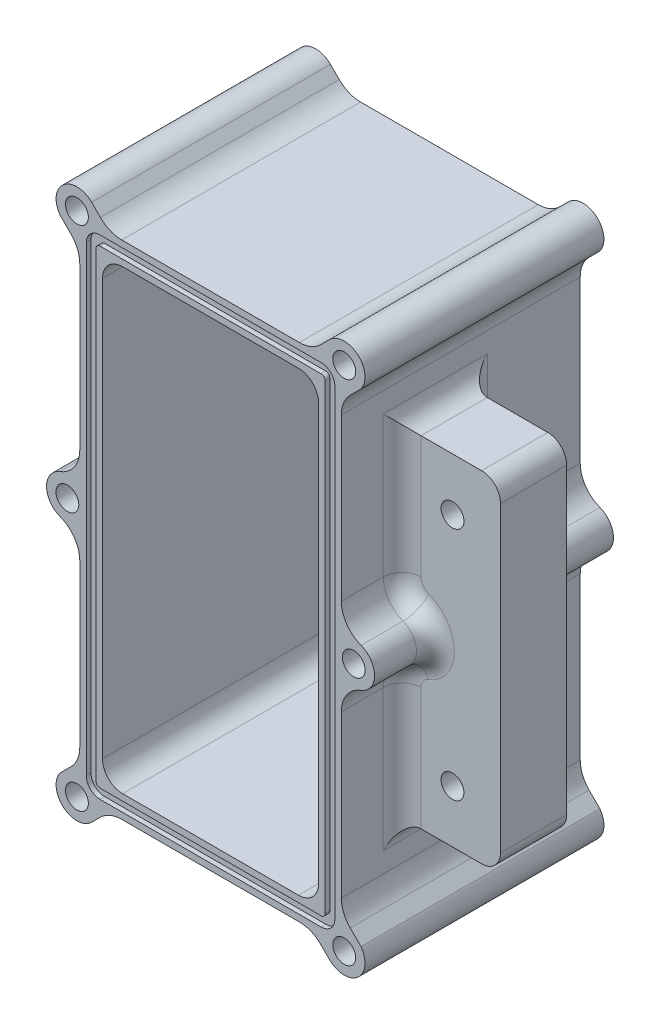
SolidWorks part; units mm, degrees
material "ABS"
ref_plane "X-Y Datum" through (0, 0, 0) normal (0, 0, 1) x (1, 0, 0)
ref_plane "X-Z Datum" through (0, 0, 0) normal (0, 1, 0) x (1, 0, 0)
ref_plane "Y-Z Datum" through (0, 0, 0) normal (1, 0, 0) x (0, 0, -1)
sketch "Sketch2" plane through (0, 0, 0) normal (0, 0, 1) x (1, 0, 0)
  line L1 (-28.575, 60.325) -> (28.575, 60.325)
  line L2 (-28.575, 60.325) -> (-28.575, -60.325)
  line L3 (-28.575, -60.325) -> (28.575, -60.325)
  line L4 (28.575, 60.325) -> (28.575, -60.325)
  line L5 (-28.575, 60.325) -> (28.575, -60.325) construction
  line L6 (-28.575, -60.325) -> (28.575, 60.325) construction
  point P0 (0, 0)
  dimension "D1" = 57.15
  dimension "D2" = 120.65
extrude "Boss-Extrude1" add sketch "Sketch2" along normal mid plane 57.15
shell "Shell1" thickness 6 removed face at (0, 0, 28.575) outward yes
sketch "Sketch3" plane through (0, 0, -28.575) normal (0, 0, 1) x (1, 0, 0)
  line L4 (28.575, -60.325) -> (28.575, 60.325)
  line L5 (28.575, 60.325) -> (-28.575, 60.325)
  line L6 (-28.575, 60.325) -> (-28.575, -60.325)
  line L7 (-28.575, -60.325) -> (28.575, -60.325)
  line L8 (28.575, -60.325) -> (28.575, 60.325)
  line L9 (28.575, 60.325) -> (-28.575, 60.325)
  line L10 (-28.575, 60.325) -> (-28.575, -60.325)
  line L11 (-28.575, -60.325) -> (28.575, -60.325)
  dimension "D1" = 0
extrude "Cut-Extrude1" cut sketch "Sketch3" against normal blind 50.8
fillet "Fillet1" radius 5.334 8 edges at (-34.575, -66.325, -3) (34.575, -66.325, -3) (34.575, 66.325, -3) (-34.575, 66.325, -3) (-28.575, -60.325, -3) (28.575, -60.325, -3) (-28.575, 60.325, -3) (28.575, 60.325, -3)
sketch "Sketch5" plane through (0, 0, -34.575) normal (0, 0, -1) x (-1, 0, 0)
  line L19 (-29.241, -64.6077) -> (29.241, -64.6077)
  line L20 (32.8577, -60.991) -> (32.8577, 60.991)
  line L21 (29.241, 64.6077) -> (-29.241, 64.6077)
  line L22 (-32.8577, 60.991) -> (-32.8577, -60.991)
  line L23 (-29.241, -63.325) -> (29.241, -63.325)
  line L24 (31.575, -60.991) -> (31.575, 60.991)
  line L25 (29.241, 63.325) -> (-29.241, 63.325)
  line L26 (-31.575, 60.991) -> (-31.575, -60.991)
  line L27 (-29.241, -63.325) -> (29.241, -63.325) construction
  line L28 (31.575, -60.991) -> (31.575, 60.991) construction
  line L29 (29.241, 63.325) -> (-29.241, 63.325) construction
  line L30 (-31.575, 60.991) -> (-31.575, -60.991) construction
  line L31 (-30.2923, 60.991) -> (-30.2923, -60.991)
  line L32 (-29.241, -62.0423) -> (29.241, -62.0423)
  line L33 (30.2923, -60.991) -> (30.2923, 60.991)
  line L34 (29.241, 62.0423) -> (-29.241, 62.0423)
  arc A17 (29.241, -64.6077) -> (32.8577, -60.991) centre (29.241, -60.991) ccw
  arc A18 (32.8577, 60.991) -> (29.241, 64.6077) centre (29.241, 60.991) ccw
  arc A19 (-29.241, 64.6077) -> (-32.8577, 60.991) centre (-29.241, 60.991) ccw
  arc A20 (-32.8577, -60.991) -> (-29.241, -64.6077) centre (-29.241, -60.991) ccw
  arc A21 (-31.575, -60.991) -> (-29.241, -63.325) centre (-29.241, -60.991) ccw
  arc A22 (29.241, -63.325) -> (31.575, -60.991) centre (29.241, -60.991) ccw
  arc A23 (31.575, 60.991) -> (29.241, 63.325) centre (29.241, 60.991) ccw
  arc A24 (-29.241, 63.325) -> (-31.575, 60.991) centre (-29.241, 60.991) ccw
  arc A25 (-31.575, -60.991) -> (-29.241, -63.325) centre (-29.241, -60.991) ccw construction
  arc A26 (29.241, -63.325) -> (31.575, -60.991) centre (29.241, -60.991) ccw construction
  arc A27 (31.575, 60.991) -> (29.241, 63.325) centre (29.241, 60.991) ccw construction
  arc A28 (-29.241, 63.325) -> (-31.575, 60.991) centre (-29.241, 60.991) ccw construction
  arc A29 (-29.241, 62.0423) -> (-30.2923, 60.991) centre (-29.241, 60.991) ccw
  arc A30 (-30.2923, -60.991) -> (-29.241, -62.0423) centre (-29.241, -60.991) ccw
  arc A31 (29.241, -62.0423) -> (30.2923, -60.991) centre (29.241, -60.991) ccw
  arc A32 (30.2923, 60.991) -> (29.241, 62.0423) centre (29.241, 60.991) ccw
  dimension "D1" = 3
  dimension "D2" = 1.2827
  dimension "D3" = 1.2827
extrude "Cut-Extrude2" cut sketch "Sketch5" against normal blind 1.2446
ref_plane "Plane1" through (0, 0, -3) normal (0, 0, 1) x (1, 0, 0)
sketch "Sketch6" plane through (0, 0, -34.575) normal (0, 0, -1) x (-1, 0, 0)
  line L0 (29.9844, 61.7344) -> (31.7984, 63.5484)
  line L1 (31.7984, 63.5484) -> (35.3339, 67.0839)
  line L2 (39.7675, 63.8292) -> (34.575, 58.6367)
  line L3 (34.575, 60.991) -> (34.575, -60.991) construction
  line L4 (31.4448, 70.973) -> (26.7968, 66.325)
  line L5 (-29.241, 66.325) -> (29.241, 66.325) construction
  line L10 (-29.241, -66.325) -> (29.241, -66.325)
  line L11 (34.575, -60.991) -> (34.575, 60.991)
  line L12 (29.241, 66.325) -> (-29.241, 66.325)
  line L13 (-34.575, 60.991) -> (-34.575, -60.991)
  line L14 (-29.241, -66.325) -> (29.241, -66.325)
  line L15 (34.575, -60.991) -> (34.575, 60.991)
  line L16 (29.241, 66.325) -> (-29.241, 66.325)
  line L17 (-34.575, 60.991) -> (-34.575, -60.991)
  arc A0 (30.2923, 60.991) -> (29.241, 62.0423) centre (29.241, 60.991) ccw construction
  arc A1 (32.8577, 60.991) -> (29.241, 64.6077) centre (29.241, 60.991) ccw construction
  circle A2 centre (35.3339, 67.0839) radius 3.025
  circle A3 centre (35.3339, 67.0839) radius 5.5
  arc A8 (29.241, -66.325) -> (34.575, -60.991) centre (29.241, -60.991) ccw
  arc A9 (34.575, 60.991) -> (29.241, 66.325) centre (29.241, 60.991) ccw
  arc A10 (-29.241, 66.325) -> (-34.575, 60.991) centre (-29.241, 60.991) ccw
  arc A11 (-34.575, -60.991) -> (-29.241, -66.325) centre (-29.241, -60.991) ccw
  arc A12 (29.241, -66.325) -> (34.575, -60.991) centre (29.241, -60.991) ccw
  arc A13 (34.575, 60.991) -> (29.241, 66.325) centre (29.241, 60.991) ccw
  arc A14 (-29.241, 66.325) -> (-34.575, 60.991) centre (-29.241, 60.991) ccw
  arc A15 (-34.575, -60.991) -> (-29.241, -66.325) centre (-29.241, -60.991) ccw
  line M13 (34.575, -60.991) -> (34.575, 60.991)
  arc M14 (34.575, 60.991) -> (29.241, 66.325) centre (29.241, 60.991) ccw
  line M15 (29.241, 66.325) -> (-29.241, 66.325)
  dimension "D1" = 6.05
  dimension "D2" = 11
  dimension "D3" = 5
  dimension "D4" = 0
extrude "Boss-Extrude2" add sketch "Sketch6" against normal up to surface (63.15 mm away) contours A3 A2 L2 M14 | A2 | A3 L4 M15 M14 | A3 L2 M14 M13 region at (-28.991, 67.5661, -34.575) region at (-34.2091, 69.7996, -34.575) region at (-30.2605, 68.7642, -34.575) region at (-35.7481, 60.7435, -34.575) up to face at (0, 0, 28.575)
sketch "Sketch7" plane through (0, 0, -34.575) normal (0, 0, -1) x (-1, 0, 0)
  line L0 (31.4448, 70.973) -> (26.7968, 66.325) construction
  line L1 (39.7675, 63.8292) -> (34.575, 58.6367) construction
  line L2 (29.9844, 61.7344) -> (31.7984, 63.5484) construction
  line L3 (31.7984, 63.5484) -> (35.3339, 67.0839) construction
  line L4 (-34.575, 60.991) -> (-34.575, -60.991)
  line L5 (-29.241, -66.325) -> (29.241, -66.325)
  line L6 (34.575, -60.991) -> (34.575, 60.991)
  line L7 (29.241, 66.325) -> (-29.241, 66.325)
  line L8 (-34.575, 60.991) -> (-34.575, -60.991)
  line L9 (-29.241, -66.325) -> (29.241, -66.325)
  line L10 (34.575, -60.991) -> (34.575, 60.991)
  line L11 (29.241, 66.325) -> (-29.241, 66.325)
  line L12 (31.4448, 70.973) -> (26.7968, 66.325)
  line L13 (39.7675, 63.8292) -> (34.575, 58.6367)
  line L14 (29.9844, 61.7344) -> (31.7984, 63.5484)
  line L15 (31.7984, 63.5484) -> (35.3339, 67.0839)
  circle A1 centre (35.3339, 67.0839) radius 5.5
  circle A2 centre (35.3339, 67.0839) radius 5.5
  circle A3 centre (35.3339, 67.0839) radius 3.025
  circle A4 centre (35.3339, 67.0839) radius 3.025
  arc A8 (-34.575, -60.991) -> (-29.241, -66.325) centre (-29.241, -60.991) ccw
  arc A9 (29.241, -66.325) -> (34.575, -60.991) centre (29.241, -60.991) ccw
  arc A10 (34.575, 60.991) -> (29.241, 66.325) centre (29.241, 60.991) ccw
  arc A11 (-29.241, 66.325) -> (-34.575, 60.991) centre (-29.241, 60.991) ccw
  arc A12 (-34.575, -60.991) -> (-29.241, -66.325) centre (-29.241, -60.991) ccw
  arc A13 (29.241, -66.325) -> (34.575, -60.991) centre (29.241, -60.991) ccw
  arc A14 (34.575, 60.991) -> (29.241, 66.325) centre (29.241, 60.991) ccw
  arc A15 (-29.241, 66.325) -> (-34.575, 60.991) centre (-29.241, 60.991) ccw
  dimension "D1" = 0
  dimension "D2" = 0
  dimension "D3" = 0
extrude "Cut-Extrude3" cut sketch "Sketch7" against normal blind 10 contours A4 region at (-34.2091, 69.7996, -34.575)
mirror "Mirror2" about plane through (0, 0, 0) normal (1, 0, 0) of "Cut-Extrude3", "Boss-Extrude2"
mirror "Mirror3" about plane through (0, 0, 0) normal (0, 1, 0) of "Mirror2"
sketch "Sketch8" plane through (0, 0, -34.575) normal (0, 0, -1) x (-1, 0, 0)
  line L0 (32.8577, 0) -> (34.575, 0)
  line L1 (32.8577, -60.991) -> (32.8577, 60.991) construction
  line L2 (34.575, 58.6367) -> (34.575, -58.6367) construction
  line L3 (34.575, 0) -> (37.8577, 0)
  line L4 (32.8577, -60.991) -> (32.8577, 60.991) construction
  line L5 (37.8577, 5.5) -> (34.575, 5.5)
  line L6 (37.8577, -5.5) -> (34.575, -5.5)
  line L7 (34.575, 58.6367) -> (34.575, -58.6367)
  circle A0 centre (37.8577, 0) radius 3.025
  circle A1 centre (37.8577, 0) radius 5.5
  line M7 (34.575, -58.6367) -> (34.575, 58.6367)
  dimension "D1" = 6.05
  dimension "D2" = 11
  dimension "D3" = 5
extrude "Boss-Extrude3" add sketch "Sketch8" against normal up to surface (63.15 mm away) contours A1 L5 L7 | A1 A0 L7 M7 | A0 | A1 L6 M7 region at (-37.8577, 2.9394, -34.575) region at (-34.7158, 2.2065, -34.575) region at (-35.3786, 5.1803, -34.575) region at (-35.3786, -5.1803, -34.575) up to face at (0, 0, 28.575)
sketch "Sketch9" plane through (0, 0, -34.575) normal (0, 0, -1) x (-1, 0, 0)
  line L0 (34.575, 58.6367) -> (34.575, -58.6367) construction
  line L1 (37.8577, -5.5) -> (34.575, -5.5) construction
  line L2 (37.8577, 5.5) -> (34.575, 5.5) construction
  line L3 (32.8577, 0) -> (34.575, 0) construction
  line L4 (34.575, 0) -> (37.8577, 0) construction
  line L5 (34.575, 58.6367) -> (34.575, -58.6367)
  line L6 (37.8577, -5.5) -> (34.575, -5.5)
  line L7 (37.8577, 5.5) -> (34.575, 5.5)
  line L8 (32.8577, 0) -> (34.575, 0)
  line L9 (34.575, 0) -> (37.8577, 0)
  circle A1 centre (37.8577, 0) radius 5.5
  circle A2 centre (37.8577, 0) radius 5.5
  circle A3 centre (37.8577, 0) radius 3.025
  circle A4 centre (37.8577, 0) radius 3.025
  dimension "D1" = 0
  dimension "D2" = 0
extrude "Cut-Extrude4" cut sketch "Sketch9" against normal blind 10 contours A4 region at (-37.8577, 2.9394, -34.575)
mirror "Mirror4" about plane through (0, 0, 0) normal (1, 0, 0) of "Cut-Extrude4", "Boss-Extrude3"
mirror "Mirror6" about plane through (0, 0, -3) normal (0, 0, 1) of "Cut-Extrude2"
sketch "Sketch10" plane through (0, 0, 28.575) normal (0, 0, 1) x (1, 0, 0)
  line L0 (-29.9844, 61.7344) -> (-31.7984, 63.5484) construction
  line L1 (-31.7984, 63.5484) -> (-35.3339, 67.0839) construction
  line L2 (-31.4448, 70.973) -> (-26.7968, 66.325) construction
  line L3 (-39.7675, 63.8292) -> (-34.575, 58.6367) construction
  line L4 (-34.575, 60.991) -> (-34.575, -60.991)
  line L5 (-29.241, -66.325) -> (29.241, -66.325)
  line L6 (34.575, -60.991) -> (34.575, 60.991)
  line L7 (29.241, 66.325) -> (-29.241, 66.325)
  line L8 (-34.575, 60.991) -> (-34.575, -60.991)
  line L9 (-29.241, -66.325) -> (29.241, -66.325)
  line L10 (34.575, -60.991) -> (34.575, 60.991)
  line L11 (29.241, 66.325) -> (-29.241, 66.325)
  line L12 (-29.9844, 61.7344) -> (-31.7984, 63.5484)
  line L13 (-31.7984, 63.5484) -> (-35.3339, 67.0839)
  line L14 (-31.4448, 70.973) -> (-26.7968, 66.325)
  line L15 (-39.7675, 63.8292) -> (-34.575, 58.6367)
  circle A1 centre (-35.3339, 67.0839) radius 3.025
  circle A2 centre (-35.3339, 67.0839) radius 3.025
  circle A3 centre (-35.3339, 67.0839) radius 5.5
  circle A4 centre (-35.3339, 67.0839) radius 5.5
  arc A8 (-34.575, -60.991) -> (-29.241, -66.325) centre (-29.241, -60.991) ccw
  arc A9 (29.241, -66.325) -> (34.575, -60.991) centre (29.241, -60.991) ccw
  arc A10 (34.575, 60.991) -> (29.241, 66.325) centre (29.241, 60.991) ccw
  arc A11 (-29.241, 66.325) -> (-34.575, 60.991) centre (-29.241, 60.991) ccw
  arc A12 (-34.575, -60.991) -> (-29.241, -66.325) centre (-29.241, -60.991) ccw
  arc A13 (29.241, -66.325) -> (34.575, -60.991) centre (29.241, -60.991) ccw
  arc A14 (34.575, 60.991) -> (29.241, 66.325) centre (29.241, 60.991) ccw
  arc A15 (-29.241, 66.325) -> (-34.575, 60.991) centre (-29.241, 60.991) ccw
  dimension "D1" = 0
  dimension "D2" = 0
  dimension "D3" = 0
extrude "Cut-Extrude5" cut sketch "Sketch10" against normal blind 10 contours A2 region at (-38.0496, 68.2088, 28.575)
mirror "Mirror9" about plane through (0, 0, 0) normal (1, 0, 0) of "Cut-Extrude5"
mirror "Mirror10" about plane through (0, 0, 0) normal (0, 1, 0) of "Mirror9"
sketch "Sketch11" plane through (0, 0, 28.575) normal (0, 0, 1) x (1, 0, 0)
  line L0 (-32.8577, 0) -> (-34.575, 0) construction
  line L1 (-34.575, 0) -> (-37.8577, 0) construction
  line L2 (-37.8577, 5.5) -> (-34.575, 5.5) construction
  line L3 (-37.8577, -5.5) -> (-34.575, -5.5) construction
  line L4 (-34.575, 58.6367) -> (-34.575, -58.6367) construction
  line L5 (-32.8577, 0) -> (-34.575, 0)
  line L6 (-34.575, 0) -> (-37.8577, 0)
  line L7 (-37.8577, 5.5) -> (-34.575, 5.5)
  line L8 (-37.8577, -5.5) -> (-34.575, -5.5)
  line L9 (-34.575, 58.6367) -> (-34.575, -58.6367)
  circle A1 centre (-37.8577, 0) radius 3.025
  circle A2 centre (-37.8577, 0) radius 3.025
  circle A3 centre (-37.8577, 0) radius 5.5
  circle A4 centre (-37.8577, 0) radius 5.5
  dimension "D1" = 0
  dimension "D2" = 0
extrude "Cut-Extrude6" cut sketch "Sketch11" against normal blind 10 contours A2 region at (-40.7971, 0, 28.575)
mirror "Mirror11" about plane through (0, 0, 0) normal (1, 0, 0) of "Cut-Extrude6"
fillet "Fillet2" radius 8 12 edges at (-34.575, 5.5, -3) (-34.575, -5.5, -3) (-34.575, -58.6367, -3) (-26.7968, -66.325, -3) (26.7968, -66.325, -3) (34.575, -58.6367, -3) (34.575, -5.5, -3) (34.575, 5.5, -3) (34.575, 58.6367, -3) (26.7968, 66.325, -3) (-26.7968, 66.325, -3) (-34.575, 58.6367, -3)
ref_plane "Plane2" through (0, 0, -5) normal (0, 0, 1) x (1, 0, 0)
sketch "Sketch13" plane through (0, 0, -5) normal (0, 0, 1) x (1, 0, 0)
  line L0 (60.575, 0) -> (34.575, 0) construction
  line L1 (34.575, -45) -> (60.575, -45)
  line L2 (34.575, -45) -> (34.575, 45)
  line L3 (34.575, 45) -> (60.575, 45)
  line L4 (60.575, -45) -> (60.575, 45)
  line L5 (47.875, -31.075) -> (47.875, 31.075) construction
  line L14 (-23.4831, -66.325) -> (23.4831, -66.325)
  line L15 (-31.4448, -70.973) -> (-29.14, -68.6681)
  line L16 (-36.9181, -60.9798) -> (-39.7675, -63.8292)
  line L17 (-34.575, -12.649) -> (-34.575, -55.323)
  line L18 (-34.575, 55.323) -> (-34.575, 12.649)
  line L19 (-39.7675, 63.8292) -> (-36.9181, 60.9798)
  line L20 (-29.14, 68.6681) -> (-31.4448, 70.973)
  line L21 (23.4831, 66.325) -> (-23.4831, 66.325)
  line L22 (31.4448, 70.973) -> (29.14, 68.6681)
  line L23 (36.9181, 60.9798) -> (39.7675, 63.8292)
  line L24 (34.575, 12.649) -> (34.575, 55.323)
  line L25 (34.575, -55.323) -> (34.575, -12.649)
  line L26 (39.7675, -63.8292) -> (36.9181, -60.9798)
  line L27 (29.14, -68.6681) -> (31.4448, -70.973)
  line L28 (-23.4831, -66.325) -> (23.4831, -66.325)
  line L29 (-31.4448, -70.973) -> (-29.14, -68.6681)
  line L30 (-36.9181, -60.9798) -> (-39.7675, -63.8292)
  line L31 (-34.575, -12.649) -> (-34.575, -55.323)
  line L32 (-34.575, 55.323) -> (-34.575, 12.649)
  line L33 (-39.7675, 63.8292) -> (-36.9181, 60.9798)
  line L34 (-29.14, 68.6681) -> (-31.4448, 70.973)
  line L35 (23.4831, 66.325) -> (-23.4831, 66.325)
  line L36 (31.4448, 70.973) -> (29.14, 68.6681)
  line L37 (36.9181, 60.9798) -> (39.7675, 63.8292)
  line L38 (34.575, 12.649) -> (34.575, 55.323)
  line L39 (34.575, -55.323) -> (34.575, -12.649)
  line L40 (39.7675, -63.8292) -> (36.9181, -60.9798)
  line L41 (29.14, -68.6681) -> (31.4448, -70.973)
  circle A0 centre (47.875, -31.075) radius 3.025
  circle A1 centre (47.875, 31.075) radius 3.025
  arc A18 (-23.4831, -66.325) -> (-29.14, -68.6681) centre (-23.4831, -74.325) ccw
  arc A19 (-39.7675, -63.8292) -> (-31.4448, -70.973) centre (-35.3339, -67.0839) ccw
  arc A20 (-36.9181, -60.9798) -> (-34.575, -55.323) centre (-42.575, -55.323) ccw
  arc A21 (-34.575, -12.649) -> (-39.7796, -5.1533) centre (-42.575, -12.649) ccw
  arc A22 (-39.7796, 5.1533) -> (-39.7796, -5.1533) centre (-37.8577, 0) ccw
  arc A23 (-39.7796, 5.1533) -> (-34.575, 12.649) centre (-42.575, 12.649) ccw
  arc A24 (-34.575, 55.323) -> (-36.9181, 60.9798) centre (-42.575, 55.323) ccw
  arc A25 (-31.4448, 70.973) -> (-39.7675, 63.8292) centre (-35.3339, 67.0839) ccw
  arc A26 (-29.14, 68.6681) -> (-23.4831, 66.325) centre (-23.4831, 74.325) ccw
  arc A27 (23.4831, 66.325) -> (29.14, 68.6681) centre (23.4831, 74.325) ccw
  arc A28 (39.7675, 63.8292) -> (31.4448, 70.973) centre (35.3339, 67.0839) ccw
  arc A29 (36.9181, 60.9798) -> (34.575, 55.323) centre (42.575, 55.323) ccw
  arc A30 (34.575, 12.649) -> (39.7796, 5.1533) centre (42.575, 12.649) ccw
  arc A31 (39.7796, -5.1533) -> (39.7796, 5.1533) centre (37.8577, 0) ccw
  arc A32 (39.7796, -5.1533) -> (34.575, -12.649) centre (42.575, -12.649) ccw
  arc A33 (34.575, -55.323) -> (36.9181, -60.9798) centre (42.575, -55.323) ccw
  arc A34 (31.4448, -70.973) -> (39.7675, -63.8292) centre (35.3339, -67.0839) ccw
  arc A35 (29.14, -68.6681) -> (23.4831, -66.325) centre (23.4831, -74.325) ccw
  arc A36 (-23.4831, -66.325) -> (-29.14, -68.6681) centre (-23.4831, -74.325) ccw
  arc A37 (-39.7675, -63.8292) -> (-31.4448, -70.973) centre (-35.3339, -67.0839) ccw
  arc A38 (-36.9181, -60.9798) -> (-34.575, -55.323) centre (-42.575, -55.323) ccw
  arc A39 (-34.575, -12.649) -> (-39.7796, -5.1533) centre (-42.575, -12.649) ccw
  arc A40 (-39.7796, 5.1533) -> (-39.7796, -5.1533) centre (-37.8577, 0) ccw
  arc A41 (-39.7796, 5.1533) -> (-34.575, 12.649) centre (-42.575, 12.649) ccw
  arc A42 (-34.575, 55.323) -> (-36.9181, 60.9798) centre (-42.575, 55.323) ccw
  arc A43 (-31.4448, 70.973) -> (-39.7675, 63.8292) centre (-35.3339, 67.0839) ccw
  arc A44 (-29.14, 68.6681) -> (-23.4831, 66.325) centre (-23.4831, 74.325) ccw
  arc A45 (23.4831, 66.325) -> (29.14, 68.6681) centre (23.4831, 74.325) ccw
  arc A46 (39.7675, 63.8292) -> (31.4448, 70.973) centre (35.3339, 67.0839) ccw
  arc A47 (36.9181, 60.9798) -> (34.575, 55.323) centre (42.575, 55.323) ccw
  arc A48 (34.575, 12.649) -> (39.7796, 5.1533) centre (42.575, 12.649) ccw
  arc A49 (39.7796, -5.1533) -> (39.7796, 5.1533) centre (37.8577, 0) ccw
  arc A50 (39.7796, -5.1533) -> (34.575, -12.649) centre (42.575, -12.649) ccw
  arc A51 (34.575, -55.323) -> (36.9181, -60.9798) centre (42.575, -55.323) ccw
  arc A52 (31.4448, -70.973) -> (39.7675, -63.8292) centre (35.3339, -67.0839) ccw
  arc A53 (29.14, -68.6681) -> (23.4831, -66.325) centre (23.4831, -74.325) ccw
  point P51 (47.875, 0)
  dimension "D5" = 6.05
  dimension "D2" = 90
  dimension "D3" = 26
  dimension "D4" = 62.15
  dimension "D6" = 12.7
  dimension "D1" = 0
extrude "Boss-Extrude4" add sketch "Sketch13" along normal blind 17.5 contours A49 A50 L2 L1 L4 L3 A48 A1 A0 region at (48.0137, 0, -5)
fillet "Fillet3" radius 5 14 edges at (34.575, -28.8245, 12.5) (36.0037, -8.0863, 12.5) (43.3577, 0, 12.5) (36.0037, 8.0863, 12.5) (34.575, -28.8245, -5) (36.0037, -8.0863, -5) (43.3577, 0, -5) (36.0037, 8.0863, -5) (34.575, -45, 3.75) (34.575, 28.8245, 12.5) (34.575, 45, 3.75) (34.575, 28.8245, -5) (60.575, -45, 3.75) (60.575, 45, 3.75)
